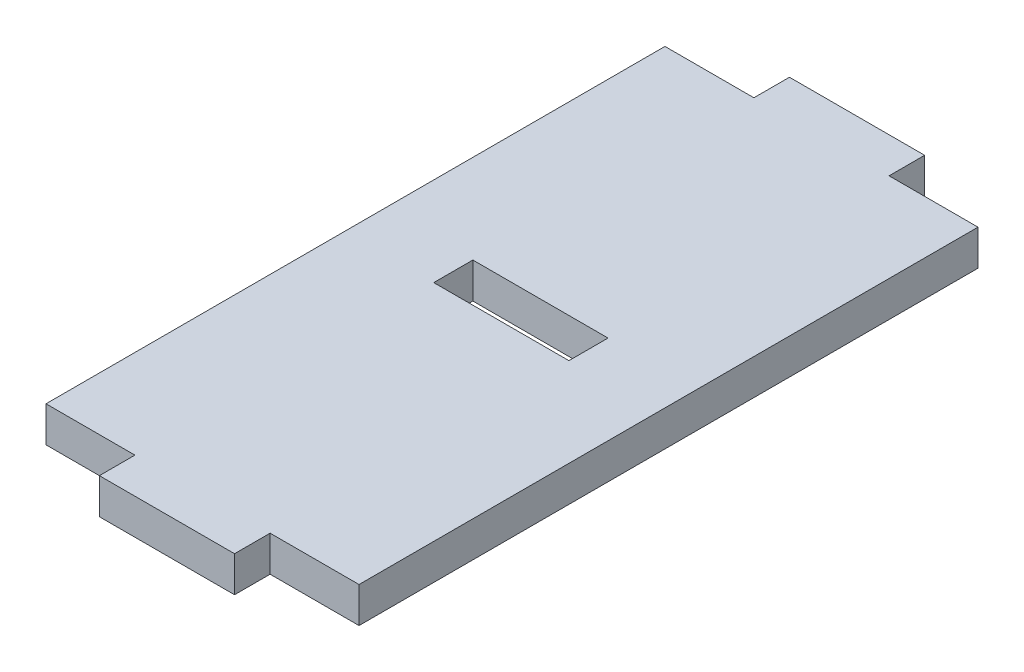
SolidWorks part; units mm, degrees
ref_plane "前视基准面" through (0, 0, 0) normal (0, 0, 1) x (1, 0, 0)
ref_plane "上视基准面" through (0, 0, 0) normal (0, 1, 0) x (1, 0, 0)
ref_plane "右视基准面" through (0, 0, 0) normal (1, 0, 0) x (0, 0, -1)
sketch "草图1" plane through (0, 0, 0) normal (0, 1, 0) x (1, 0, 0)
  line L0 (-2, -2) -> (19.6, -2) construction
  line L1 (0, 0) -> (17.6, 0)
  line L2 (0, 0) -> (0, 34.8)
  line L3 (0, 34.8) -> (17.6, 34.8)
  line L4 (17.6, 0) -> (17.6, 34.8)
  line L5 (19.6, -2) -> (19.6, 36.8) construction
  line L6 (-2, 36.8) -> (19.6, 36.8) construction
  line L7 (-2, -2) -> (-2, 36.8) construction
  line L8 (12.6, 5) -> (12.6, 29.8) construction
  line L9 (5, 29.8) -> (12.6, 29.8) construction
  line L10 (5, 5) -> (5, 29.8) construction
  line L11 (5, 5) -> (12.6, 5) construction
  line L12 (12.6, 5) -> (12.6, -4.6272) construction
  line L13 (5, 5) -> (5, -2) construction
  line L14 (-6.6019, 16.8) -> (28.6178, 16.8) construction
  line L15 (5, 0) -> (12.6, 0)
  line L16 (5, 0) -> (5, -2)
  line L17 (5, -2) -> (12.6, -2)
  line L18 (12.6, 0) -> (12.6, -2)
  line L19 (5, 36.8) -> (12.6, 36.8)
  line L20 (5, 36.8) -> (5, 34.8)
  line L21 (5, 34.8) -> (12.6, 34.8)
  line L22 (12.6, 36.8) -> (12.6, 34.8)
  line L23 (-6.6019, 19) -> (28.6178, 19) construction
  line L24 (-6.6019, 16.8) -> (28.6178, 16.8) construction
  line L25 (5, 19) -> (12.6, 19)
  line L26 (5, 19) -> (5, 16.8)
  line L27 (5, 16.8) -> (12.6, 16.8)
  line L28 (12.6, 19) -> (12.6, 16.8)
  point P27 (0, 0)
  point P34 (0, 0)
  point P35 (0, 0)
  point P37 (0, 0)
  dimension "D1" = 2
  dimension "D2" = 5
  dimension "D3" = 2.2
extrude "凸台-拉伸1" add sketch "草图1" along normal blind 2 contours L1 L4 L3 L2 L25 L28 L27 L26 | L18 L1 L16 L17 | L22 L19 L20 L3 region at (0.39, 0, -17.4) region at (8.8, 0, 1) region at (8.8, 0, -35.8)
